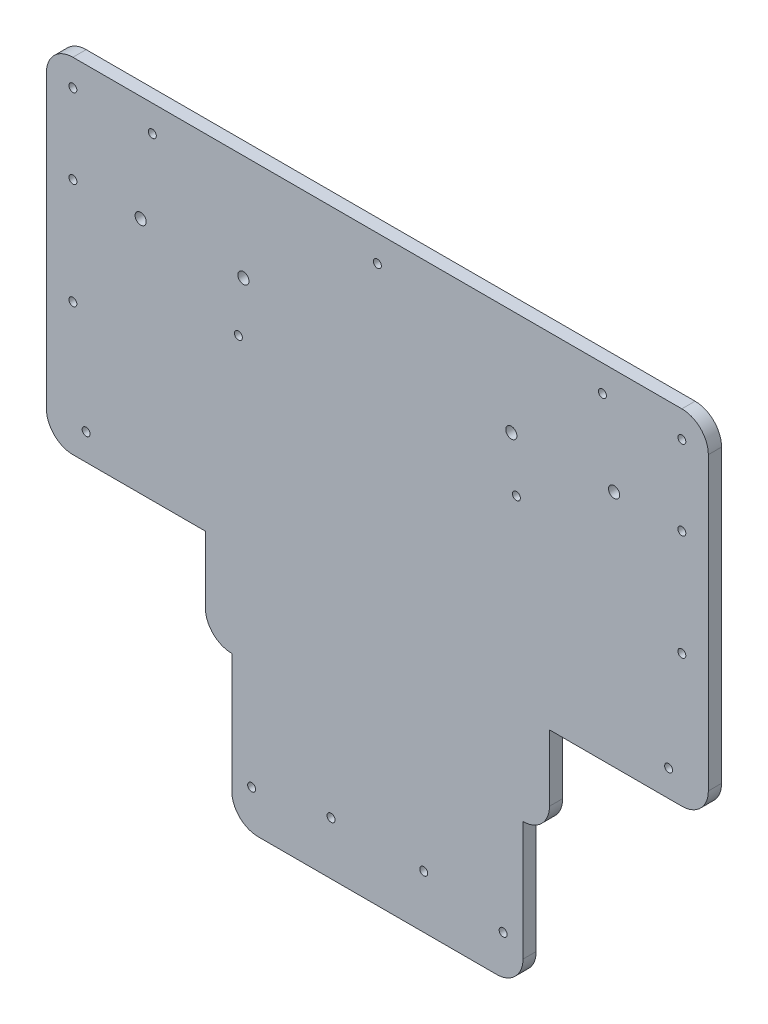
SolidWorks part; units mm, degrees
ref_plane "前视基准面" through (0, 0, 0) normal (0, 0, 1) x (1, 0, 0)
ref_plane "上视基准面" through (0, 0, 0) normal (0, 1, 0) x (1, 0, 0)
ref_plane "右视基准面" through (0, 0, 0) normal (1, 0, 0) x (0, 0, -1)
sketch "草图1" plane through (0, 0, 0) normal (0, 0, 1) x (1, 0, 0)
  line L1 (10, 0) -> (240, 0)
  line L2 (0, -10) -> (0, -210)
  line L3 (10, -220) -> (240, -220)
  line L4 (250, -10) -> (250, -210)
  arc A0 (0, -210) -> (10, -220) centre (10, -210) ccw
  arc A1 (240, -220) -> (250, -210) centre (240, -210) ccw
  arc A2 (240, 0) -> (250, -10) centre (240, -10) cw
  arc A3 (10, 0) -> (0, -10) centre (10, -10) ccw
  point P9 (250, -220)
  point P12 (250, 0)
  point P15 (0, 0)
  dimension "D3" = 10
  dimension "D1" = 250
  dimension "D2" = 220
extrude "凸台-拉伸1" add sketch "草图1" along normal blind 5
sketch "草图7" plane through (0, 0, 0) normal (0, 0, -1) x (-1, 0, 0)
  line L0 (-35.6, -40) -> (0, -40) construction
  line L1 (0, -10) -> (0, -210) construction
  line L2 (-35.6, -40) -> (-35.6, -64.4792) construction
  line L3 (-74.4, -40) -> (-74.4, -67.314) construction
  line L6 (-125, 0) -> (-125, -220) construction
  line L7 (-240, 0) -> (-10, 0) construction
  line L8 (-10, -220) -> (-240, -220) construction
  circle A0 centre (-74.4, -40) radius 2.1 construction
  circle A1 centre (-74.4, -40) radius 2.1
  circle A2 centre (-35.6, -40) radius 2.1 construction
  circle A3 centre (-35.6, -40) radius 2.1
  circle A4 centre (-214.4, -40) radius 2.1
  circle A5 centre (-175.6, -40) radius 2.1
sketch "草图9" plane through (0, 0, 5) normal (0, 0, 1) x (1, 0, 0)
  circle A0 centre (40, -10) radius 1.5 construction
  circle A1 centre (40, -10) radius 1.5
  circle A2 centre (125, -10) radius 1.5 construction
  circle A3 centre (125, -10) radius 1.5
  circle A4 centre (210, -10) radius 1.5 construction
  circle A5 centre (210, -10) radius 1.5
extrude "切除-拉伸7" cut sketch "草图9" against normal up to surface (5 mm away) up to face at (125, -110, 0)
extrude "切除-拉伸8" cut sketch "草图7" against normal up to surface (5 mm away) up to face at (41.5, -10, 5)
sketch "草图10" plane through (0, 0, 5) normal (0, 0, 1) x (1, 0, 0)
  line L0 (250, -210) -> (250, -10) construction
  line L1 (250, -130) -> (190, -130)
  line L2 (250, -130) -> (250, -220)
  line L3 (250, -220) -> (190, -220)
  line L4 (190, -130) -> (190, -220)
  line L5 (10, -220) -> (240, -220) construction
  line L6 (125, 0) -> (125, -235.6988) construction
  line L7 (240, 0) -> (10, 0) construction
  line L8 (60, -130) -> (60, -220)
  line L9 (0, -220) -> (60, -220)
  line L10 (0, -130) -> (0, -220)
  line L11 (0, -130) -> (60, -130)
  dimension "D1" = 60
  dimension "D2" = 90
extrude "切除-拉伸9" cut sketch "草图10" against normal up to next
sketch "草图11" plane through (0, 0, 5) normal (0, 0, 1) x (1, 0, 0)
  line L0 (60, -210) -> (60, -220)
  line L1 (60, -220) -> (70, -220)
  line L2 (190, -210) -> (190, -220)
  line L3 (190, -130) -> (190, -220) construction
  line L4 (60, -220) -> (190, -220) construction
  line L5 (190, -220) -> (180, -220)
  line L6 (0, -120) -> (0, -130)
  line L7 (0, -130) -> (10, -130)
  line L8 (190, -220) -> (190, -130)
  line L9 (190, -130) -> (250, -130)
  line L10 (250, -130) -> (250, -10)
  line L11 (240, 0) -> (10, 0)
  line L12 (0, -10) -> (0, -130)
  line L13 (0, -130) -> (60, -130)
  line L14 (60, -130) -> (60, -220)
  line L15 (60, -220) -> (190, -220)
  line L16 (190, -210) -> (190, -130)
  line L17 (190, -130) -> (240, -130)
  line L18 (250, -120) -> (250, -10)
  line L19 (240, 0) -> (10, 0)
  line L20 (0, -10) -> (0, -120)
  line L21 (10, -130) -> (60, -130)
  line L22 (60, -130) -> (60, -210)
  line L23 (70, -220) -> (180, -220)
  line L24 (250, -120) -> (250, -130)
  line L25 (250, -130) -> (240, -130)
  arc A0 (190, -210) -> (180, -220) centre (180, -210) cw
  arc A1 (60, -210) -> (70, -220) centre (70, -210) ccw
  arc A2 (250, -10) -> (240, 0) centre (240, -10) ccw
  arc A3 (10, 0) -> (0, -10) centre (10, -10) ccw
  arc A4 (250, -10) -> (240, 0) centre (240, -10) ccw
  arc A5 (10, 0) -> (0, -10) centre (10, -10) ccw
  arc A6 (240, -130) -> (250, -120) centre (240, -120) ccw
  arc A7 (0, -120) -> (10, -130) centre (10, -120) ccw
  line M11 (190, -220) -> (190, -130)
  line M12 (190, -130) -> (250, -130)
  line M13 (250, -130) -> (250, -10)
  line M17 (0, -10) -> (0, -130)
  line M18 (0, -130) -> (60, -130)
  line M19 (60, -130) -> (60, -220)
  line M20 (60, -220) -> (190, -220)
  dimension "D2" = 10
  dimension "D3" = 10
  dimension "D1" = 0
extrude "切除-拉伸11" cut sketch "草图11" against normal up to next contours A7 M17 M18 | A1 M19 M20 | A0 M11 M20 | A6 M12 M13 region at (62.2337, -217.7663, 5) region at (2.2337, -127.7663, 5) region at (187.7663, -217.7663, 5) region at (247.7663, -127.7663, 5)
sketch "草图12" plane through (0, 0, 5) normal (0, 0, 1) x (1, 0, 0)
  line L0 (177.5, 0.2469) -> (177.5, -59.7531) construction
  line L1 (177.5, -59.7531) -> (54.2607, -59.7531) construction
  line L2 (162.5, -159) -> (162.5, 30) construction
  line L3 (125, 0) -> (125, -86.6219) construction
  line L4 (240, 0) -> (10, 0) construction
  circle A0 centre (177.5, -59.7531) radius 1.5
  circle A1 centre (142.5, -200) radius 1.5 construction
  circle A2 centre (142.5, -200) radius 1.5
  circle A3 centre (72.5, -59.7531) radius 1.5
  circle A4 centre (107.5, -200) radius 1.5
  dimension "D3" = 3
  dimension "D1" = 60
  dimension "D2" = 15
extrude "切除-拉伸12" cut sketch "草图12" against normal up to next
sketch "草图13" plane through (0, 0, 0) normal (0, 0, -1) x (-1, 0, 0)
  circle A0 centre (-77.5, -205) radius 1.5 construction
  circle A1 centre (-77.5, -205) radius 1.5
  circle A2 centre (-172.5, -205) radius 1.5 construction
  circle A3 centre (-172.5, -205) radius 1.5
  circle A4 centre (-240, -10) radius 1.5 construction
  circle A5 centre (-240, -10) radius 1.5
  circle A6 centre (-10, -10) radius 1.5 construction
  circle A7 centre (-10, -10) radius 1.5
extrude "切除-拉伸13" cut sketch "草图13" against normal up to next
sketch "草图14" plane through (0, 0, 5) normal (0, 0, 1) x (1, 0, 0)
  line L0 (240, -10) -> (240, -122.5975) construction
  line L1 (240, -130) -> (240, -80) construction
  line L2 (240, -130) -> (190, -130) construction
  line L3 (240, -130) -> (240, -40) construction
  line L4 (125, 0) -> (125, -220) construction
  line L5 (240, 0) -> (10, 0) construction
  line L6 (70, -220) -> (180, -220) construction
  circle A0 centre (240, -40) radius 1.5
  circle A1 centre (240, -80) radius 1.5
  circle A2 centre (10, -80) radius 1.5
  circle A3 centre (10, -40) radius 1.5
  dimension "D3" = 3
  dimension "D4" = 3
  dimension "D1" = 50
  dimension "D2" = 90
extrude "切除-拉伸14" cut sketch "草图14" against normal blind 10
sketch "草图15" plane through (0, 0, 5) normal (0, 0, 1) x (1, 0, 0)
  circle A0 centre (235, -120) radius 1.5 construction
  circle A1 centre (235, -120) radius 1.5
  circle A2 centre (15, -120) radius 1.5 construction
  circle A3 centre (15, -120) radius 1.5
extrude "切除-拉伸15" cut sketch "草图15" against normal up to next
sketch "草图16" plane through (0, 0, 5) normal (0, 0, 1) x (1, 0, 0)
  line L0 (60, -210) -> (60, -130) construction
  line L1 (60, -165) -> (70, -165)
  line L2 (60, -165) -> (60, -220)
  line L3 (60, -220) -> (70, -220)
  line L4 (70, -165) -> (70, -220)
  line L5 (125, -220) -> (125, -165) construction
  line L6 (70, -220) -> (180, -220) construction
  line L7 (190, -220) -> (180, -220)
  line L8 (180, -165) -> (180, -220)
  line L9 (190, -165) -> (180, -165)
  line L10 (190, -165) -> (190, -220)
  dimension "D1" = 55
extrude "切除-拉伸16" cut sketch "草图16" against normal blind 10
fillet "圆角3" radius 10 2 edges at (180, -220, 2.5) (70, -220, 2.5)
fillet "圆角4" radius 10 2 edges at (190, -165, 2.5) (60, -165, 2.5)
